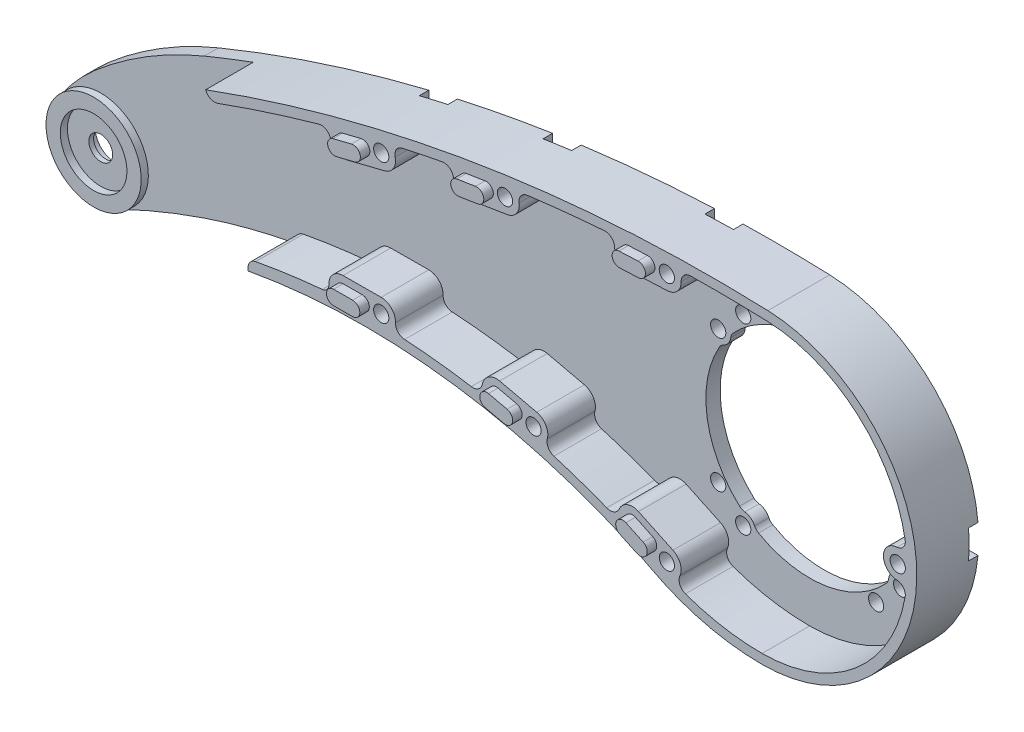
SolidWorks part; units mm, degrees
material "6061-T6 (SS)"
ref_plane "前视基准面" through (0, 0, 0) normal (0, 0, 1) x (1, 0, 0)
ref_plane "上视基准面" through (0, 0, 0) normal (0, 1, 0) x (1, 0, 0)
ref_plane "右视基准面" through (0, 0, 0) normal (1, 0, 0) x (0, 0, -1)
other "Configuration Table"
sketch "草图1" plane through (0, 0, 0) normal (0, 0, 1) x (1, 0, 0)
  line L0 (-74.3846, 0) -> (17.4339, 0) construction
  line L1 (0, 31.8895) -> (0, -25.7876) construction
  line L2 (0, 0) -> (19.2142, 13.9599) construction
  line L3 (0, 0) -> (13.9599, 19.2142) construction
  line L4 (0, 0) -> (-148.9161, -18) construction
  line L6 (0, 0) -> (-1.2281, 22.9672) construction
  line L8 (-1.2281, 22.9672) -> (-150.1441, 4.9672) construction
  line L9 (-150.1441, 4.9672) -> (-148.9161, -18) construction
  line L10 (-148.9161, -18) -> (-97.5528, -158.9319)
  line L12 (0, 0) -> (-103.1063, -167.9797) construction
  arc A116 (16.0762, 14.724) -> (-10.7394, 18.9712) centre (0, 0) ccw
  circle A117 centre (0, 0) radius 23.75 construction
  circle A118 centre (19.2142, 13.9599) radius 1.6
  circle A119 centre (13.9599, 19.2142) radius 1.6
  circle A120 centre (19.2142, -13.9599) radius 1.6
  circle A121 centre (13.9599, -19.2142) radius 1.6
  circle A122 centre (-13.9599, -19.2142) radius 1.6
  circle A123 centre (-19.2142, -13.9599) radius 1.6
  circle A124 centre (-19.2142, 13.9599) radius 1.6
  circle A125 centre (-13.9599, 19.2142) radius 1.6
  arc A126 (0, -32.5) -> (1.2171, 32.4772) centre (0, 0) ccw
  arc A127 (-157.1671, -12.3502) -> (-144.5702, -27.0063) centre (-148.9161, -18) ccw
  arc A134 (-28.3708, -24.2609) -> (-127.3793, -19.9637) centre (-83.3912, -149.2082) ccw
  arc A135 (-127.3793, -19.9637) -> (-144.5702, -27.0063) centre (-78.0965, -164.7651) ccw
  arc A136 (1.2171, 32.4772) -> (-127.1723, 9.5805) centre (-10.2849, -274.4361) ccw
  arc A138 (-23.6381, -26.5665) -> (-28.3708, -24.2609) centre (-55.9067, -86.7929) ccw
  arc A139 (0, -32.5) -> (-23.6381, -26.5665) centre (0, 17.5518) cw
  arc A140 (16.5853, 13.6255) -> (18.0838, 11.5631) centre (19.2142, 13.9599) ccw
  arc A141 (16.5853, 13.6255) -> (16.0762, 14.724) centre (14.6013, 13.3732) ccw
  arc A142 (18.0838, 11.5631) -> (18.9712, 10.7394) centre (17.2307, 9.7541) cw
  arc A143 (11.5631, -18.0838) -> (10.7394, -18.9712) centre (9.7541, -17.2307) cw
  arc A144 (13.6255, -16.5853) -> (11.5631, -18.0838) centre (13.9599, -19.2142) ccw
  arc A145 (13.6255, -16.5853) -> (14.724, -16.0762) centre (13.3732, -14.6013) ccw
  arc A146 (-18.0838, -11.5631) -> (-18.9712, -10.7394) centre (-17.2307, -9.7541) cw
  arc A147 (-16.5853, -13.6255) -> (-18.0838, -11.5631) centre (-19.2142, -13.9599) ccw
  arc A148 (-16.5853, -13.6255) -> (-16.0762, -14.724) centre (-14.6013, -13.3732) ccw
  arc A149 (-11.5631, 18.0838) -> (-10.7394, 18.9712) centre (-9.7541, 17.2307) cw
  arc A150 (-13.6255, 16.5853) -> (-11.5631, 18.0838) centre (-13.9599, 19.2142) ccw
  arc A151 (-13.6255, 16.5853) -> (-14.724, 16.0762) centre (-13.3732, 14.6013) ccw
  arc A152 (-16.0762, -14.724) -> (10.7394, -18.9712) centre (0, 0) ccw
  arc A153 (14.724, -16.0762) -> (18.9712, 10.7394) centre (0, 0) ccw
  arc A154 (-14.724, 16.0762) -> (-18.9712, -10.7394) centre (0, 0) ccw
  arc A155 (-127.1723, 9.5805) -> (-150.1438, -4.5112) centre (-94.9478, -68.7195) ccw
  arc A156 (-150.1438, -4.5112) -> (-157.1671, -12.3502) centre (-123.7132, -35.2574) ccw
  arc A157 (11.5631, 18.0838) -> (10.7394, 18.9712) centre (9.7541, 17.2307) ccw
  arc A158 (11.5631, 18.0838) -> (13.6255, 16.5853) centre (13.9599, 19.2142) ccw
  arc A159 (13.6255, 16.5853) -> (14.724, 16.0762) centre (13.3732, 14.6013) cw
  arc A160 (16.5853, -13.6255) -> (16.0762, -14.724) centre (14.6013, -13.3732) cw
  arc A161 (18.0838, -11.5631) -> (16.5853, -13.6255) centre (19.2142, -13.9599) ccw
  arc A162 (18.0838, -11.5631) -> (18.9712, -10.7394) centre (17.2307, -9.7541) ccw
  arc A163 (-13.6255, -16.5853) -> (-14.724, -16.0762) centre (-13.3732, -14.6013) cw
  arc A164 (-11.5631, -18.0838) -> (-13.6255, -16.5853) centre (-13.9599, -19.2142) ccw
  arc A165 (-11.5631, -18.0838) -> (-10.7394, -18.9712) centre (-9.7541, -17.2307) ccw
  arc A166 (-16.5853, 13.6255) -> (-16.0762, 14.724) centre (-14.6013, 13.3732) cw
  arc A167 (-18.0838, 11.5631) -> (-16.5853, 13.6255) centre (-19.2142, 13.9599) ccw
  arc A168 (-18.0838, 11.5631) -> (-18.9712, 10.7394) centre (-17.2307, 9.7541) ccw
  arc A169 (18.9712, 10.7394) -> (16.0762, 14.724) centre (0, 0) ccw
  arc A170 (-10.7394, 18.9712) -> (-14.724, 16.0762) centre (0, 0) ccw
  arc A171 (10.7394, -18.9712) -> (14.724, -16.0762) centre (0, 0) ccw
  arc A172 (-16.0762, -14.724) -> (-18.9712, -10.7394) centre (0, 0) cw
  point P27 (0, 0)
  point P73 (0, 0)
  point P83 (0, 0)
  point P105 (0, 0)
  dimension "D1" = 43.6
  dimension "D3" = 36
  dimension "D4" = 3.2
  dimension "D2" = 47.5
  dimension "D6" = 3.2
  dimension "D8" = 65
  dimension "D15" = 20
  dimension "D16" = 5.3
  dimension "D17" = 2
  dimension "D5" = 18
  dimension "D9" = 18
  dimension "D10" = 150
  dimension "D11" = 23
  dimension "D12" = 150
  dimension "D13" = 103.132
  dimension "D14" = 51.566
  dimension "D19" = 2
  dimension "D7" = 4
  dimension "D18" = 4
  dimension "D20" = 4
extrude "凸台-拉伸1" add sketch "草图1" along normal blind 3 contours A135 A134 A138 A126 A127 A125 A124 A123 A122 A121 A120 A119 A118 A116 | A168 A167 A166 A154 | A158 A159 A116 A157 | A162 A161 A160 A153 | A165 A164 A163 A152 region at (12.6444, 17.4035, 0) region at (17.4035, -12.6444, 0) region at (-17.4035, 12.6444, 0) region at (-12.6444, -17.4035, 0) region at (-60.0806, 1.6127, 0)
sketch "草图2" plane through (0, 0, 0) normal (0, 0, -1) x (-1, 0, 0)
  line L0 (-28.5, 0) -> (0, 0) construction
  line L2 (0, 0) -> (18.5599, 13.5842) construction
  line L3 (18.5599, 13.5842) -> (167.476, -4.4158) construction
  line L4 (167.476, -4.4158) -> (148.9161, -18) construction
  line L5 (148.9161, -18) -> (10.6983, -76.2738) construction
  line L7 (25.351, 15.2815) -> (162.3611, -1.2794) construction
  line L9 (24.751, 10.3176) -> (161.7611, -6.2433) construction
  line L11 (19.8643, 25.54) -> (27.8561, 25.1781)
  line L13 (18.7235, -21.0787) -> (25.9631, -17.6745)
  line L16 (53.5282, 22.5613) -> (61.4287, 21.3032)
  line L17 (79.2716, 17.6568) -> (87.0322, 15.7143)
  line L19 (80.013, -5.7241) -> (88.0129, -5.7588)
  line L20 (47.3274, -10.2892) -> (55.1237, -8.4956)
  arc A111 (-1.1422, 30.4786) -> (-30.0624, 5.1483) centre (0, 0) ccw
  arc A112 (0, -30.5) -> (16.1065, -27.7202) centre (0, 17.5518) ccw
  arc A114 (75.0886, -10.9322) -> (61.0732, -12.4928) centre (83.3912, -149.2082) ccw
  arc A115 (106.3649, -12.407) -> (92.3731, -10.4659) centre (78.0965, -164.7651) ccw
  arc A116 (144.5702, -27.0063) -> (157.1671, -12.3502) centre (148.9161, -18) ccw
  arc A118 (157.1671, -12.3502) -> (150.1438, -4.5112) centre (123.7132, -35.2574) ccw
  arc A119 (127.1723, 9.5805) -> (-1.2171, 32.4772) centre (10.2849, -274.4361) ccw
  arc A120 (-1.2171, 32.4772) -> (0, -32.5) centre (0, 0) ccw
  arc A121 (-1.0673, 28.48) -> (0, -28.5) centre (0, 0) ccw construction
  arc A122 (0, -32.5) -> (23.6381, -26.5665) centre (0, 17.5518) ccw
  arc A123 (28.3708, -24.2609) -> (23.6381, -26.5665) centre (55.9067, -86.7929) ccw
  arc A124 (127.3793, -19.9637) -> (28.3708, -24.2609) centre (83.3912, -149.2082) ccw
  arc A125 (144.5702, -27.0063) -> (127.3793, -19.9637) centre (78.0965, -164.7651) ccw
  arc A126 (144.5702, -27.0063) -> (157.1671, -12.3502) centre (148.9161, -18) ccw
  arc A128 (127.1723, 9.5805) -> (-1.2171, 32.4772) centre (10.2849, -274.4361) ccw
  arc A129 (-1.2171, 32.4772) -> (0, -32.5) centre (0, 0) ccw
  arc A130 (0, -32.5) -> (23.6381, -26.5665) centre (0, 17.5518) ccw
  arc A131 (28.3708, -24.2609) -> (23.6381, -26.5665) centre (55.9067, -86.7929) ccw
  arc A132 (127.3793, -19.9637) -> (28.3708, -24.2609) centre (83.3912, -149.2082) ccw
  arc A133 (144.5702, -27.0063) -> (127.3793, -19.9637) centre (78.0965, -164.7651) ccw
  arc A134 (0, -28.5) -> (21.749, -23.0407) centre (0, 17.5518) ccw construction
  arc A135 (26.7587, -20.6001) -> (21.749, -23.0407) centre (55.9067, -86.7929) ccw construction
  arc A136 (128.6681, -16.177) -> (26.7587, -20.6001) centre (83.3912, -149.2082) ccw construction
  arc A137 (146.3086, -23.4038) -> (128.6681, -16.177) centre (78.0965, -164.7651) ccw construction
  arc A138 (146.3086, -23.4038) -> (153.7238, -14.4104) centre (148.9161, -18) ccw construction
  arc A139 (153.7238, -14.4104) -> (126.0955, 5.6977) centre (120.8678, -30.5198) ccw construction
  arc A140 (126.0955, 5.6977) -> (-1.0673, 28.48) centre (10.2849, -274.4361) ccw construction
  arc A141 (-28.3421, -2.9958) -> (-28.3421, 2.9958) centre (-28.5, 0) ccw
  arc A142 (-28.3421, 2.9958) -> (-30.0624, 5.1483) centre (-28.2451, 4.837) cw
  arc A143 (-28.3421, -2.9958) -> (-30.0624, -5.1483) centre (-28.2451, -4.837) ccw
  arc A144 (-30.0624, -5.1483) -> (0, -30.5) centre (0, 0) ccw
  circle A145 centre (-28.5, 0) radius 1.6
  arc A146 (-1.1422, 30.4786) -> (0, -30.5) centre (0, 0) ccw construction
  circle A147 centre (18.5599, 13.5842) radius 7 construction
  circle A148 centre (167.476, -4.4158) radius 6 construction
  arc A149 (17.0011, 28.6182) -> (19.8643, 25.54) centre (20, 28.5369) ccw
  arc A150 (27.8561, 25.1781) -> (30.9858, 27.985) centre (27.9918, 28.175) ccw
  arc A151 (17.0011, 28.6182) -> (15.0491, 30.6555) centre (15.0181, 28.672) ccw
  arc A152 (30.9858, 27.985) -> (33.1139, 29.8374) centre (32.9655, 27.8593) cw
  arc A153 (15.0491, 30.6555) -> (-1.1422, 30.4786) centre (10.2849, -274.4361) ccw
  circle A154 centre (20, 28.5369) radius 1.6
  arc A155 (126.6313, 7.6402) -> (-1.1422, 30.4786) centre (10.2849, -274.4361) ccw construction
  arc A156 (17.2617, -25.019) -> (18.7235, -21.0787) centre (20, -23.7935) cw
  arc A157 (25.9631, -17.6745) -> (30.0023, -19.2201) centre (27.2396, -20.3894) cw
  circle A158 centre (20, -23.7935) radius 1.6
  arc A159 (17.2617, -25.019) -> (16.1065, -27.7202) centre (15.4362, -25.8359) cw
  arc A160 (30.0023, -19.2201) -> (32.6241, -20.3211) centre (31.8778, -18.4263) ccw
  circle A161 centre (54, 25.524) radius 1.6
  arc A162 (27.5648, -22.4305) -> (22.6935, -24.8036) centre (55.9067, -86.7929) ccw construction
  arc A163 (0, -30.5) -> (22.6935, -24.8036) centre (0, 17.5518) ccw construction
  arc A164 (128.0237, -18.0703) -> (27.5648, -22.4305) centre (83.3912, -149.2082) ccw construction
  arc A165 (51.0293, 25.9419) -> (53.5282, 22.5613) centre (54, 25.524) ccw
  arc A166 (61.4287, 21.3032) -> (64.8541, 23.7404) centre (61.9005, 24.2659) ccw
  arc A167 (51.0293, 25.9419) -> (49.3187, 28.1856) centre (49.0649, 26.2183) ccw
  arc A168 (64.8541, 23.7404) -> (67.177, 25.3419) centre (66.8071, 23.393) cw
  arc A169 (49.3187, 28.1856) -> (33.1139, 29.8374) centre (10.2849, -274.4361) ccw
  circle A170 centre (80, 20.567) radius 1.6
  arc A171 (77.077, 21.2425) -> (79.2716, 17.6568) centre (80, 20.567) ccw
  arc A172 (87.0322, 15.7143) -> (90.6571, 17.8435) centre (87.7606, 18.6246) ccw
  arc A173 (77.077, 21.2425) -> (75.5687, 23.6269) centre (75.1443, 21.6892) ccw
  arc A175 (75.5687, 23.6269) -> (67.177, 25.3419) centre (10.2849, -274.4361) ccw
  circle A176 centre (48, -13.2128) radius 1.6
  circle A177 centre (80, -8.7241) radius 1.6
  arc A178 (45.1049, -13.9993) -> (47.3274, -10.2892) centre (48, -13.2128) cw
  arc A180 (45.1049, -13.9993) -> (43.7228, -16.4844) centre (43.1397, -14.5332) cw
  arc A182 (43.7228, -16.4844) -> (32.6241, -20.3211) centre (83.3912, -149.2082) ccw
  arc A183 (77.0018, -8.8285) -> (80.013, -5.7241) centre (80, -8.7241) cw
  arc A184 (88.0129, -5.7588) -> (90.9971, -8.8891) centre (87.9999, -8.7587) cw
  arc A185 (77.0018, -8.8285) -> (75.0886, -10.9322) centre (74.9666, -8.8993) cw
  arc A186 (90.9971, -8.8891) -> (92.3731, -10.4659) centre (92.5129, -8.9551) ccw
  arc A187 (106.3649, -12.407) -> (107.9278, -14.9061) centre (106, -14.3735) cw
  arc A188 (145.4394, -25.205) -> (128.0237, -18.0703) centre (78.0965, -164.7651) ccw construction
  arc A190 (145.4394, -25.205) -> (155.4422, -13.3729) centre (148.9161, -18) ccw construction
  arc A191 (75.5687, 23.6269) -> (93.1109, 19.2362) centre (10.2849, -274.4361) cw construction
  arc A192 (90.6571, 17.8435) -> (93.1109, 19.2362) centre (92.5724, 17.327) cw
  arc A193 (155.4422, -13.3729) -> (126.6313, 7.6402) centre (120.8678, -30.5198) ccw construction
  arc A194 (15.0491, 30.6555) -> (33.1139, 29.8374) centre (10.2849, -274.4361) cw construction
  arc A195 (49.3187, 28.1856) -> (67.177, 25.3419) centre (10.2849, -274.4361) cw construction
  arc A196 (93.1109, 19.2362) -> (114.3181, 12.4099) centre (10.2849, -274.4361) cw
  arc A197 (114.3181, 12.4099) -> (116.8779, 13.6021) centre (115, 14.2901) ccw
  arc A198 (55.1237, -8.4956) -> (58.7441, -10.8615) centre (55.7963, -11.4192) cw
  arc A199 (58.7441, -10.8615) -> (61.0732, -12.4928) centre (60.745, -10.4829) ccw
  arc A207 (157.1671, -12.3502) -> (127.1723, 9.5805) centre (120.8678, -30.5198) ccw construction
  arc A208 (157.1671, -12.3502) -> (150.1438, -4.5112) centre (123.7132, -35.2574) ccw
  arc A209 (150.1438, -4.5112) -> (127.1723, 9.5805) centre (94.9478, -68.7195) ccw
  arc A210 (150.1438, -4.5112) -> (127.1723, 9.5805) centre (94.9478, -68.7195) ccw
  point P113 (16.5105, -418.9921)
  point P135 (90.8781, -8.8827)
  point P136 (107.9278, -14.9061)
  arc M20 (127.1723, 9.5805) -> (-1.2171, 32.4772) centre (10.2849, -274.4361) ccw
  arc M21 (-1.2171, 32.4772) -> (0, -32.5) centre (0, 0) ccw
  arc M22 (0, -32.5) -> (23.6381, -26.5665) centre (0, 17.5518) ccw
  arc M23 (23.6381, -26.5665) -> (28.3708, -24.2609) centre (55.9067, -86.7929) cw
  arc M24 (28.3708, -24.2609) -> (127.3793, -19.9637) centre (83.3912, -149.2082) cw
  arc M25 (127.3793, -19.9637) -> (144.5702, -27.0063) centre (78.0965, -164.7651) cw
  dimension "D7" = 150
  dimension "D9" = 14
  dimension "D11" = 12
  dimension "D12" = 150
  dimension "D13" = 8
  dimension "D10" = 2.5
  dimension "D8" = 166.66
  dimension "D14" = 20
  dimension "D15" = 8
  dimension "D16" = 8
  dimension "D17" = 8
  dimension "D18" = 54
  dimension "D19" = 80
  dimension "D20" = 8
  dimension "D21" = 48
  dimension "D22" = 80
  dimension "D23" = 8
  dimension "D6" = 23
  dimension "D25" = 106
  dimension "D26" = 2
  dimension "D27" = 115
  dimension "D28" = 20
  dimension "D4" = 6
  dimension "D5" = 3.2
  dimension "D24" = 2
  dimension "D1" = 0
  dimension "D2" = 2
  dimension "D3" = 2
extrude "凸台-拉伸2" add sketch "草图2" along normal blind 10 contours M20 M21 M22 M23 M24 M25 region at (-17.9227, 26.6047, 0)
sketch "草图4" plane through (0, 0, -10) normal (0, 0, -1) x (-1, 0, 0)
  line L0 (20, 28.5369) -> (27.9918, 28.175) construction
  line L3 (61.9005, 24.2659) -> (54, 25.524) construction
  line L8 (80, 20.567) -> (87.7606, 18.6246) construction
  line L9 (20, -23.7935) -> (27.2396, -20.3894) construction
  line L10 (48, -13.2128) -> (55.7963, -11.4192) construction
  line L11 (80, -8.7241) -> (87.9999, -8.7587) construction
  line L12 (27.2396, -20.3894) -> (23.6198, -22.0915) construction
  line L15 (27.8779, -21.7468) -> (24.2581, -23.4489)
  line L24 (26.6013, -19.032) -> (22.9815, -20.734)
  line L27 (27.9918, 28.175) -> (23.9959, 28.356) construction
  line L30 (27.924, 26.6766) -> (23.9281, 26.8575)
  line L33 (28.0597, 29.6735) -> (24.0638, 29.8545)
  line L36 (61.9005, 24.2659) -> (57.9502, 24.8949) construction
  line L39 (87.7606, 18.6246) -> (83.8803, 19.5958) construction
  line L40 (87.3964, 17.1695) -> (83.5161, 18.1407)
  line L41 (88.1248, 20.0797) -> (84.2445, 21.0509)
  line L42 (87.9999, -8.7587) -> (84, -8.7414) construction
  line L43 (87.9934, -10.2587) -> (83.9935, -10.2414)
  line L44 (88.0064, -7.2587) -> (84.0065, -7.2414)
  line L45 (55.7963, -11.4192) -> (51.8982, -12.316) construction
  line L46 (56.1326, -12.881) -> (52.2345, -13.7778)
  line L47 (55.46, -9.9574) -> (51.5619, -10.8542)
  line L48 (61.6646, 22.7845) -> (57.7143, 23.4136)
  line L49 (62.1363, 25.7472) -> (58.1861, 26.3763)
  arc A24 (27.8779, -21.7468) -> (26.6013, -19.032) centre (27.2396, -20.3894) ccw
  arc A25 (22.9815, -20.734) -> (24.2581, -23.4489) centre (23.6198, -22.0915) ccw
  arc A26 (27.924, 26.6766) -> (28.0597, 29.6735) centre (27.9918, 28.175) ccw
  arc A27 (24.0638, 29.8545) -> (23.9281, 26.8575) centre (23.9959, 28.356) ccw
  arc A30 (87.3964, 17.1695) -> (88.1248, 20.0797) centre (87.7606, 18.6246) ccw
  arc A31 (84.2445, 21.0509) -> (83.5161, 18.1407) centre (83.8803, 19.5958) ccw
  arc A32 (87.9934, -10.2587) -> (88.0064, -7.2587) centre (87.9999, -8.7587) ccw
  arc A33 (84.0065, -7.2414) -> (83.9935, -10.2414) centre (84, -8.7414) ccw
  arc A34 (56.1326, -12.881) -> (55.46, -9.9574) centre (55.7963, -11.4192) ccw
  arc A35 (51.5619, -10.8542) -> (52.2345, -13.7778) centre (51.8982, -12.316) ccw
  arc A36 (61.6646, 22.7845) -> (62.1363, 25.7472) centre (61.9005, 24.2659) ccw
  arc A37 (58.1861, 26.3763) -> (57.7143, 23.4136) centre (57.9502, 24.8949) ccw
  point P12 (25.4297, -21.2404)
  point P18 (25.9939, 28.2655)
  point P24 (59.9253, 24.5804)
  point P30 (85.8204, 19.1102)
  point P36 (85.9999, -8.7501)
  point P42 (53.8473, -11.8676)
  dimension "D2" = 1.5
  dimension "D1" = 4
extrude "凸台-拉伸3" add sketch "草图4" along normal blind 2 contours L44 A33 L43 A32 | L33 A27 L30 A26 | L49 A37 L48 A36 | A30 L41 A31 L40 | A34 L47 A35 L46 | A24 L24 A25 L15 region at (-85.9999, -8.7501, -10)
sketch "草图5" plane through (0, 0, -10) normal (0, 0, -1) x (-1, 0, 0)
  circle A0 centre (80, -8.7241) radius 1.6 construction
  circle A2 centre (-28.5, 0) radius 1.6 construction
  circle A4 centre (-28.5, 0) radius 1.6
  circle A6 centre (54, 25.524) radius 1.6 construction
  circle A8 centre (80, 20.567) radius 1.6 construction
  circle A10 centre (80, -8.7241) radius 1.6
  circle A12 centre (48, -13.2128) radius 1.6 construction
  circle A14 centre (20, -23.7935) radius 1.6 construction
  circle A27 centre (20, 28.5369) radius 1.6 construction
  circle A28 centre (54, 25.524) radius 1.6
  circle A29 centre (80, 20.567) radius 1.6
  circle A31 centre (48, -13.2128) radius 1.6
  circle A32 centre (20, -23.7935) radius 1.6
  circle A33 centre (20, 28.5369) radius 1.6
extrude "切除-拉伸1" cut sketch "草图5" against normal up to next
sketch "草图10" plane through (0, 0, 0) normal (0, 0, -1) x (-1, 0, 0)
  circle A0 centre (148.9161, -18) radius 2.5
  dimension "D1" = 5
extrude "切除-拉伸4" cut sketch "草图10" against normal up to next
sketch "草图11" plane through (0, 0, 3) normal (0, 0, 1) x (1, 0, 0)
  circle A0 centre (-148.9161, -18) radius 4.15
  dimension "D1" = 8.3
extrude "切除-拉伸5" cut sketch "草图11" against normal blind 2
sketch "草图13" plane through (0, 0, 3) normal (0, 0, 1) x (1, 0, 0)
  line L0 (-83, 20.567) -> (-83, 23.9606)
  line L1 (-77, 20.567) -> (-77, 25.3591)
  line L2 (-57, 25.524) -> (-57, 29.1191)
  line L3 (-51, 25.524) -> (-51, 29.982)
  line L4 (-23, 28.5369) -> (-23, 32.4293)
  line L5 (-17, 28.5369) -> (-17, 32.6192)
  line L6 (-83, -8.7241) -> (-83, -12.6837)
  line L7 (-77, -8.7241) -> (-77, -12.8328)
  line L8 (-51, -13.2128) -> (-51, -16.5813)
  line L9 (-45, -13.2128) -> (-45, -18.1922)
  line L10 (-23, -23.7935) -> (-23, -26.9025)
  line L11 (-17, -23.7935) -> (-17, -29.5246)
  line L12 (28.5, 3) -> (32.3612, 3)
  line L13 (28.5, -3) -> (32.3612, -3)
  line L14 (28.5, 3) -> (28.5, -3) construction
  arc A0 (-83, 20.567) -> (-77, 20.567) centre (-80, 20.567) ccw
  arc A1 (-57, 25.524) -> (-51, 25.524) centre (-54, 25.524) ccw
  arc A2 (-23, 28.5369) -> (-17, 28.5369) centre (-20, 28.5369) ccw
  arc A3 (28.5, 3) -> (28.5, -3) centre (28.5, 0) ccw
  arc A5 (-45, -13.2128) -> (-51, -13.2128) centre (-48, -13.2128) ccw
  arc A7 (-23.6381, -26.5665) -> (0, -32.5) centre (0, 17.5518) ccw construction
  arc A8 (1.2171, 32.4772) -> (-127.1723, 9.5805) centre (-10.2849, -274.4361) ccw construction
  arc A9 (-28.3708, -24.2609) -> (-127.3793, -19.9637) centre (-83.3912, -149.2082) ccw construction
  arc A10 (-23.6381, -26.5665) -> (0, -32.5) centre (0, 17.5518) ccw
  arc A11 (-23.6381, -26.5665) -> (-28.3708, -24.2609) centre (-55.9067, -86.7929) ccw construction
  arc A12 (0, -32.5) -> (1.2171, 32.4772) centre (0, 0) ccw construction
  arc A13 (1.2171, 32.4772) -> (-127.1723, 9.5805) centre (-10.2849, -274.4361) ccw
  arc A15 (0, -32.5) -> (1.2171, 32.4772) centre (0, 0) ccw
  arc A16 (-23.6381, -26.5665) -> (-28.3708, -24.2609) centre (-55.9067, -86.7929) ccw
  arc A18 (-17, -23.7935) -> (-23, -23.7935) centre (-20, -23.7935) ccw
  arc A19 (-28.3708, -24.2609) -> (-127.3793, -19.9637) centre (-83.3912, -149.2082) ccw
  arc A20 (-77, -8.7241) -> (-83, -8.7241) centre (-80, -8.7241) ccw
  circle M9 centre (28.5, 0) radius 1.6
  circle M10 centre (-54, 25.524) radius 1.6
  circle M11 centre (-80, 20.567) radius 1.6
  circle M12 centre (-80, -8.7241) radius 1.6
  circle M13 centre (-48, -13.2128) radius 1.6
  circle M14 centre (-20, -23.7935) radius 1.6
  circle M15 centre (-20, 28.5369) radius 1.6
  arc M17 (-127.3793, -19.9637) -> (-28.3708, -24.2609) centre (-83.3912, -149.2082) cw
  arc M19 (-23.6381, -26.5665) -> (0, -32.5) centre (0, 17.5518) ccw
  arc M20 (0, -32.5) -> (1.2171, 32.4772) centre (0, 0) ccw
  arc M21 (1.2171, 32.4772) -> (-127.1723, 9.5805) centre (-10.2849, -274.4361) ccw
  dimension "D1" = 6
  dimension "D2" = 6
  dimension "D3" = 3
  dimension "D4" = 6
extrude "切除-拉伸6" cut sketch "草图13" against normal blind 2 contours L9 A5 L8 M17 M13 | L11 A18 L10 M19 M14 | L12 L14 L13 M9 M20 | L14 A3 M9 | L4 A2 L5 M21 M15 | L2 A1 L3 M21 M10 | L0 A0 L1 M21 M11 | L7 A20 L6 M17 M12 region at (-79.9969, -12.6323, 3) region at (-47.9649, -17.2562, 3) region at (-20.0005, -28.2147, 3) region at (30.7421, 0, 3) region at (-19.9975, 32.4462, 3) region at (-53.9885, 29.4706, 3) region at (-82.9017, 22.2638, 3) region at (28.4329, 2.3, 3)
sketch "草图14" plane through (0, 0, 0) normal (0, 0, -1) x (-1, 0, 0)
  circle A0 centre (148.9161, -18) radius 10
  circle A1 centre (148.9161, -18) radius 7
  dimension "D1" = 14
  dimension "D2" = 20
extrude "凸台-拉伸4" add sketch "草图14" along normal blind 1.5
mirror "镜向1" about plane through (0, 0, 3) normal (0, 0, 1) of bodies 139
sketch "草图15" plane through (0, 0, -12) normal (0, 0, -1) x (-1, 0, 0)
  line L1 (-35.6451, 57.1538) -> (167.8467, 57.1538)
  line L2 (-35.6451, 57.1538) -> (-35.6451, -44.9911)
  line L3 (-35.6451, -44.9911) -> (167.8467, -44.9911)
  line L4 (167.8467, 57.1538) -> (167.8467, -44.9911)
extrude "切除-拉伸7" cut sketch "草图15" against normal blind 15
